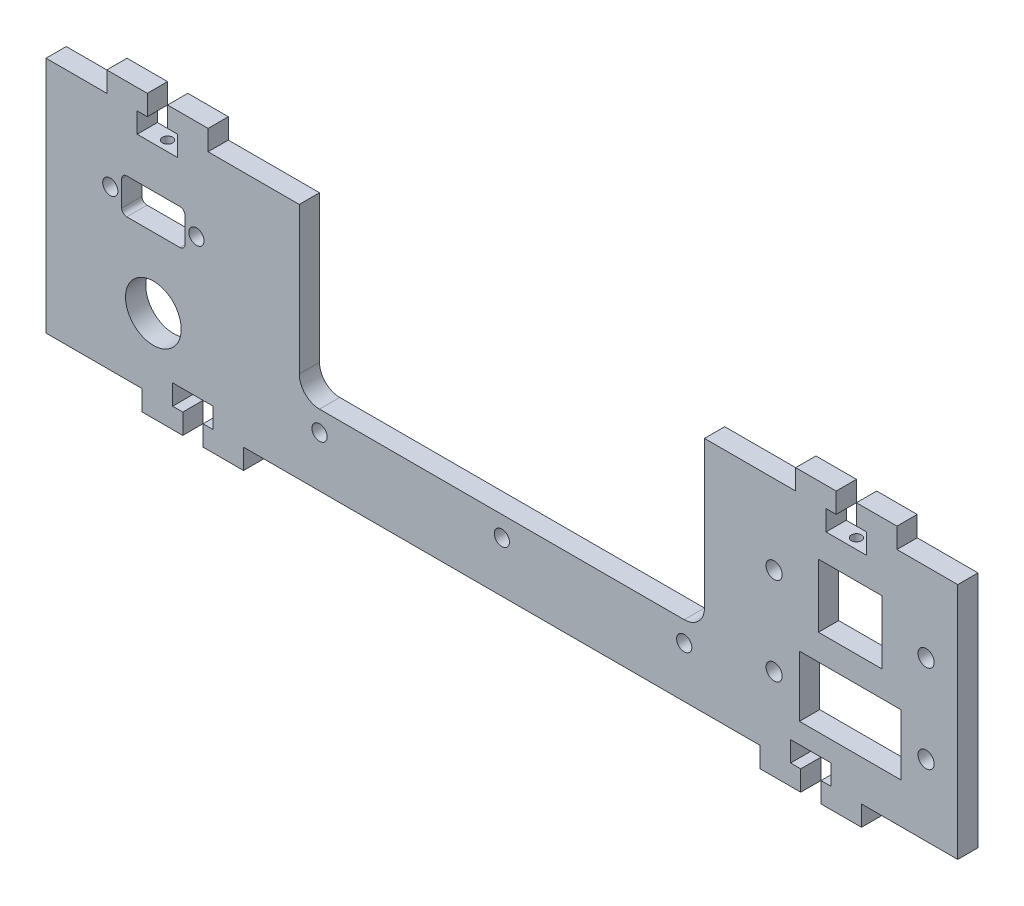
SolidWorks part; units mm, degrees
material "Ст 3 ГОСТ 380-88"
ref_plane "Спереди" through (0, 0, 0) normal (0, 0, 1) x (1, 0, 0)
ref_plane "Сверху" through (0, 0, 0) normal (0, 1, 0) x (1, 0, 0)
ref_plane "Справа" through (0, 0, 0) normal (1, 0, 0) x (0, 0, -1)
other "Configuration Table"
sketch "Эскиз1" plane through (0, 0, 0) normal (0, 0, 1) x (1, 0, 0)
  line L0 (90, -47) -> (90, 69.5201) construction
  line L1 (0, 0) -> (12, 0)
  line L2 (0, 0) -> (0, -47)
  line L3 (0, -47) -> (19, -47)
  line L4 (180, 0) -> (180, -47)
  line L6 (50, 0) -> (50, -29)
  line L7 (54, -33) -> (126, -33)
  line L8 (130, 0) -> (130, -29)
  line L10 (32, 0) -> (50, 0)
  line L11 (12, 4) -> (20, 4)
  line L12 (12, 4) -> (12, 0)
  line L13 (19, -51) -> (27, -51)
  line L14 (32, 4) -> (32, 0)
  line L15 (19, -47) -> (19, -51)
  line L16 (39, -47) -> (39, -51)
  line L17 (39, -47) -> (90, -47)
  line L18 (24, 4) -> (32, 4)
  line L20 (20, 4) -> (20, 0)
  line L22 (24, 4) -> (24, 0)
  line L23 (18, 0) -> (20, 0)
  line L24 (18, 0) -> (18, -4)
  line L25 (18, -4) -> (26, -4)
  line L26 (26, 0) -> (26, -4)
  line L27 (24, 0) -> (26, 0)
  line L28 (0, -23.5) -> (180, -23.5) construction
  line L29 (31, -51) -> (31, -47)
  line L30 (31, -47) -> (33, -47)
  line L31 (33, -47) -> (33, -43)
  line L32 (25, -43) -> (33, -43)
  line L33 (25, -47) -> (27, -47)
  line L34 (25, -47) -> (25, -43)
  line L35 (27, -51) -> (27, -47)
  line L36 (31, -51) -> (39, -51)
  line L37 (149, -51) -> (141, -51)
  line L38 (153, -51) -> (153, -47)
  line L39 (155, -47) -> (155, -43)
  line L40 (155, -47) -> (153, -47)
  line L41 (155, -43) -> (147, -43)
  line L42 (147, -47) -> (147, -43)
  line L43 (149, -47) -> (147, -47)
  line L44 (149, -51) -> (149, -47)
  line L45 (156, 0) -> (154, 0)
  line L46 (154, 0) -> (154, -4)
  line L47 (162, -4) -> (154, -4)
  line L48 (162, 0) -> (162, -4)
  line L49 (162, 0) -> (160, 0)
  line L50 (156, 4) -> (156, 0)
  line L51 (160, 4) -> (160, 0)
  line L52 (156, 4) -> (148, 4)
  line L53 (141, -47) -> (141, -51)
  line L54 (161, -47) -> (161, -51)
  line L55 (148, 4) -> (148, 0)
  line L56 (161, -51) -> (153, -51)
  line L57 (168, 4) -> (168, 0)
  line L58 (168, 4) -> (160, 4)
  line L59 (130, 0) -> (148, 0)
  line L60 (168, 0) -> (180, 0)
  line L61 (161, -47) -> (180, -47)
  line L62 (141, -47) -> (90, -47)
  line L64 (152.5, -9.3972) -> (165, -9.3972)
  line L65 (152.5, -9.3972) -> (152.5, -21.8972)
  line L66 (152.5, -21.8972) -> (165, -21.8972)
  line L67 (165, -9.3972) -> (165, -21.8972)
  line L68 (148.75, -27) -> (168.75, -27)
  line L69 (148.75, -27) -> (148.75, -39)
  line L70 (148.75, -39) -> (168.75, -39)
  line L71 (168.75, -27) -> (168.75, -39)
  line L75 (21.1944, -33) -> (21.1944, -47.8449) construction
  line L77 (7.3931, -15.6472) -> (39.75, -15.6472) construction
  line L78 (15.9444, -12.1472) -> (26.4444, -12.1472)
  line L79 (14.9444, -13.1472) -> (14.9444, -18.1472)
  line L80 (15.9444, -19.1472) -> (26.4444, -19.1472)
  line L81 (27.4444, -13.1472) -> (27.4444, -18.1472)
  arc A0 (126, -33) -> (130, -29) centre (126, -29) ccw
  arc A1 (50, -29) -> (54, -33) centre (54, -29) ccw
  circle A2 centre (143.75, -15.6472) radius 1.6
  circle A3 centre (173.75, -15.6472) radius 1.6
  circle A4 centre (143.75, -33) radius 1.6
  circle A5 centre (173.75, -33) radius 1.6
  circle A6 centre (21.1944, -33) radius 5.5
  circle A7 centre (90, -37) radius 1.5
  circle A10 centre (54, -37) radius 1.5
  circle A11 centre (126, -37) radius 1.5
  circle A12 centre (12.6944, -15.6472) radius 1.5
  circle A13 centre (29.6944, -15.6472) radius 1.5
  arc A14 (26.4444, -19.1472) -> (27.4444, -18.1472) centre (26.4444, -18.1472) ccw
  arc A15 (14.9444, -18.1472) -> (15.9444, -19.1472) centre (15.9444, -18.1472) ccw
  arc A16 (15.9444, -12.1472) -> (14.9444, -13.1472) centre (15.9444, -13.1472) ccw
  arc A17 (27.4444, -13.1472) -> (26.4444, -12.1472) centre (26.4444, -13.1472) ccw
  point P104 (14.9444, -19.1472)
  point P107 (14.9444, -12.1472)
  point P110 (27.4444, -12.1472)
  dimension "D6" = 4
  dimension "D21" = 3.2
  dimension "D22" = 3.2
  dimension "D45" = 11
  dimension "D47" = 3
  dimension "D49" = 3
  dimension "D50" = 3
  dimension "D48" = 3
  dimension "D57" = 3
  dimension "D63" = 1
  dimension "D1" = 180
  dimension "D2" = 47
  dimension "D3" = 40
  dimension "D4" = 40
  dimension "D5" = 14
  dimension "D7" = 20
  dimension "D8" = 12
  dimension "D9" = 4
  dimension "D10" = 12.5
  dimension "D11" = 4
  dimension "D12" = 8
  dimension "D13" = 2
  dimension "D14" = 2
  dimension "D15" = 4
  dimension "D16" = 4
  dimension "D17" = 12.5
  dimension "D19" = 15
  dimension "D20" = 30
  dimension "D23" = 6.25
  dimension "D24" = 8.75
  dimension "D26" = 12
  dimension "D27" = 20
  dimension "D28" = 6
  dimension "D29" = 5
  dimension "D30" = 90
  dimension "D31" = 4
  dimension "D32" = 4
  dimension "D33" = 19
  dimension "D34" = 20
  dimension "D35" = 8
  dimension "D36" = 2
  dimension "D37" = 2
  dimension "D38" = 19
  dimension "D39" = 20
  dimension "D40" = 8
  dimension "D41" = 4
  dimension "D42" = 2
  dimension "D43" = 2
  dimension "D44" = 4
  dimension "D51" = 36
  dimension "D52" = 36
  dimension "D53" = 10
  dimension "D54" = 47
  dimension "D55" = 12
  dimension "D56" = 8.5
  dimension "D58" = 8.5
  dimension "D59" = 7
  dimension "D60" = 12.5
  dimension "D61" = 3.5
  dimension "D62" = 6.25
  dimension "D64" = 14
  dimension "D25" = 2
base flange "Базовая кромка1" sketch "Эскиз1" thickness 4 reverse thickness direction no parameters "D1"=4
sketch "Эскиз6" plane through (0, 4, 0) normal (0, 1, 0) x (1, 0, 0)
  line L0 (26, 4) -> (18, 4) construction
  line L1 (20, 4) -> (20, 0) construction
  line L2 (156, 4) -> (156, 0) construction
  circle A0 centre (22, 2) radius 1
  circle A1 centre (158, 2) radius 1
  dimension "D3" = 2
  dimension "D5" = 2
  dimension "D1" = 2
  dimension "D2" = 2
  dimension "D4" = 2
extrude "Вырез-Вытянуть1" cut sketch "Эскиз6" against normal blind 10 normal cut yes
sketch "Эскиз7" plane through (0, -51, 0) normal (0, -1, 0) x (1, 0, 0)
  line L0 (25, 0) -> (33, 0) construction
  line L1 (27, -4) -> (27, 0) construction
  line L2 (149, -4) -> (149, 0) construction
  circle A0 centre (29, -2) radius 1
  circle A1 centre (151, -2) radius 1
  dimension "D1" = 2
  dimension "D4" = 2
  dimension "D2" = 2
  dimension "D3" = 2
  dimension "D5" = 2
extrude "Вырез-Вытянуть2" cut sketch "Эскиз7" against normal blind 10 normal cut yes
sketch "Сгиб-Линии1" [suppressed] plane through (0, 0, 0) normal (0, 1, 0) x (1, 0, 0)
sketch "Граничная рамка1" [suppressed] plane through (0, 0, 0) normal (0, 1, 0) x (1, 0, 0)
sheet metal parameters "Листовой металл3" thickness 4 parameters "D1"=4
flat pattern "Развертка3" [suppressed]
sketch "Сгиб-Линии2" plane through (0, 0, 0) normal (0, 1, 0) x (1, 0, 0)
sketch "Граничная рамка2" [suppressed] plane through (0, 0, 0) normal (0, 1, 0) x (1, 0, 0)
sheet metal parameters "Листовой металл4" thickness 4 parameters "D1"=4
flat pattern "Развертка3"
sketch "Сгиб-Линии2" plane through (0, 0, 0) normal (0, 1, 0) x (1, 0, 0)
sketch "Граничная рамка2" [suppressed] plane through (0, 0, 0) normal (0, 1, 0) x (1, 0, 0)
sheet metal parameters "Листовой металл5" thickness 4 parameters "D1"=4
flat pattern "Развертка3"
sketch "Сгиб-Линии2" plane through (0, 0, 0) normal (0, 1, 0) x (1, 0, 0)
sketch3d "Граничная рамка2" [suppressed]
  line L0 (-126, -22, 0) -> (54, -22, 0) construction
  line L1 (-126, 33, 0) -> (54, 33, 0) construction
  line L2 (-126, -22, 0) -> (-126, 33, 0) construction
  line L3 (54, -22, 0) -> (54, 33, 0) construction
